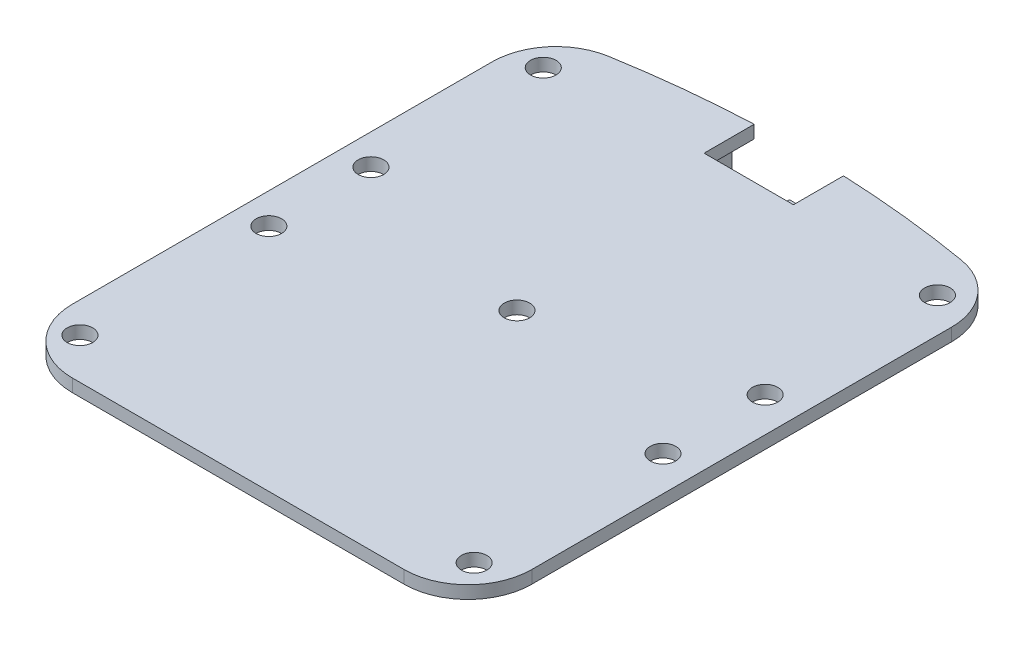
SolidWorks part; units mm, degrees
ref_plane "Front Plane" through (0, 0, 0) normal (0, 0, 1) x (1, 0, 0)
ref_plane "Top Plane" through (0, 0, 0) normal (0, 1, 0) x (1, 0, 0)
ref_plane "Right Plane" through (0, 0, 0) normal (1, 0, 0) x (0, 0, -1)
sketch "Sketch1" plane through (0, 0, 0) normal (0, 1, 0) x (1, 0, 0)
  line L1 (-64.2024, -110) -> (65.7976, -110)
  line L5 (-89.2024, -35) -> (-89.2024, -85)
  line L6 (90.7976, -35) -> (90.7976, -85)
  line L7 (-89.2024, 79.4733) -> (-89.2024, 31.4733)
  line L20 (90.7976, 31.4733) -> (90.7976, 79.4617)
  line L30 (-89.2024, -35) -> (-89.2024, 31.4733)
  line L31 (90.7976, -35) -> (90.7976, 31.4733)
  arc A0 (-68.4209, 104.1148) -> (70.0206, 104.1024) centre (0.7637, -300.0058) cw
  arc A1 (65.7976, -110) -> (90.7976, -85) centre (65.7976, -85) ccw
  arc A2 (-64.2024, -110) -> (-89.2024, -85) centre (-64.2024, -85) cw
  arc A3 (90.7976, 79.4617) -> (70.0206, 104.1024) centre (65.7976, 79.4617) ccw
  arc A4 (-89.2024, 79.4733) -> (-68.4209, 104.1148) centre (-64.2024, 79.4733) cw
  point P0 (0, 0)
  point P25 (-0.7976, 109.9942)
  dimension "D3" = 25
  dimension "D4" = 25
extrude "Boss-Extrude1" add sketch "Sketch1" along normal blind 5 contours A4 L30 A2 L1 A1 L31 A3 A0 region at (0.7967, 0, 1.3605)
sketch "Sketch5" plane through (0, 5, 0) normal (0, 1, 0) x (1, 0, 0)
  line L1 (-89.2024, -85) -> (-89.2024, 79.4733) construction
  circle A0 centre (-77.2024, 20) radius 5
  circle A1 centre (-77.2024, -20) radius 5
  circle A2 centre (-77.2024, 87.5) radius 5
  circle A3 centre (-77.2024, -94) radius 5
  circle A4 centre (0, 0) radius 5
  circle A5 centre (77.2024, -94) radius 5
  circle A6 centre (77.2024, -20) radius 5
  circle A7 centre (77.2024, 20) radius 5
  circle A8 centre (77.2024, 87.5) radius 5
  dimension "D2" = 12
  dimension "D6" = 67.5
  dimension "D8" = 10
  dimension "D5" = 12
extrude "Cut-Extrude2" cut sketch "Sketch5" against normal blind 10
sketch "Sketch6" plane through (0, 0, 0) normal (0, -1, 0) x (1, 0, 0)
  line L2 (-40, -90) -> (40, -90)
  line L3 (-40, -90) -> (-40, -10)
  line L4 (-40, -10) -> (40, -10)
  line L5 (40, -90) -> (40, -10)
  line L6 (-40, -90) -> (40, -10) construction
  line L7 (-40, -10) -> (40, -90) construction
  line L9 (-47.5, 12.5) -> (47.5, 12.5)
  line L10 (-47.5, 12.5) -> (-47.5, 107.5)
  line L11 (-47.5, 107.5) -> (47.5, 107.5)
  line L12 (47.5, 12.5) -> (47.5, 107.5)
  line L13 (-47.5, 12.5) -> (47.5, 107.5) construction
  line L14 (-47.5, 107.5) -> (47.5, 12.5) construction
  point P3 (0, -50)
  point P9 (0, 60)
  dimension "D1" = 80
  dimension "D2" = 80
  dimension "D4" = 95
  dimension "D5" = 95
extrude "Boss-Extrude2" add sketch "Sketch6" along normal blind 1
sketch "Sketch7" plane through (0, 0, 0) normal (0, -1, 0) x (1, 0, 0)
  line L3 (-40, -90) -> (40, -90) construction
  line L4 (-16.6996, -121.4032) -> (18.3004, -121.4032)
  line L5 (-16.6996, -121.4032) -> (-16.6996, -90)
  line L6 (-16.6996, -90) -> (18.3004, -90)
  line L7 (18.3004, -121.4032) -> (18.3004, -90)
  line L8 (-16.6996, -121.4032) -> (18.3004, -90) construction
  line L9 (-16.6996, -90) -> (18.3004, -121.4032) construction
  point P5 (0.8004, -105.7016)
  dimension "D1" = 35
extrude "Cut-Extrude3" cut sketch "Sketch7" against normal blind 10
sketch "Sketch8" plane through (0, 0, 0) normal (0, -1, 0) x (-1, 0, 0)
  line L1 (18.1417, 60.9282) -> (23.3362, 60.9282)
  line L2 (18.1417, 60.9282) -> (18.1417, 102.3864)
  line L3 (18.1417, 102.3864) -> (23.3362, 102.3864)
  line L4 (23.3362, 60.9282) -> (23.3362, 102.3864)
  line L5 (-21.6397, 59.2567) -> (-10.7895, 59.2567)
  line L6 (-21.6397, 59.2567) -> (-21.6397, 95.9298)
  line L7 (-21.6397, 95.9298) -> (-10.7895, 95.9298)
  line L8 (-10.7895, 59.2567) -> (-10.7895, 95.9298)
extrude "Boss-Extrude3" add sketch "Sketch8" along normal blind 44
sketch "Sketch10" plane through (10.7895, 0, 0) normal (-1, 0, 0) x (0, 0, 1)
  circle A0 centre (-82.9318, -23.4553) radius 1.6887
extrude "Boss-Extrude4" add sketch "Sketch10" along normal blind 30
